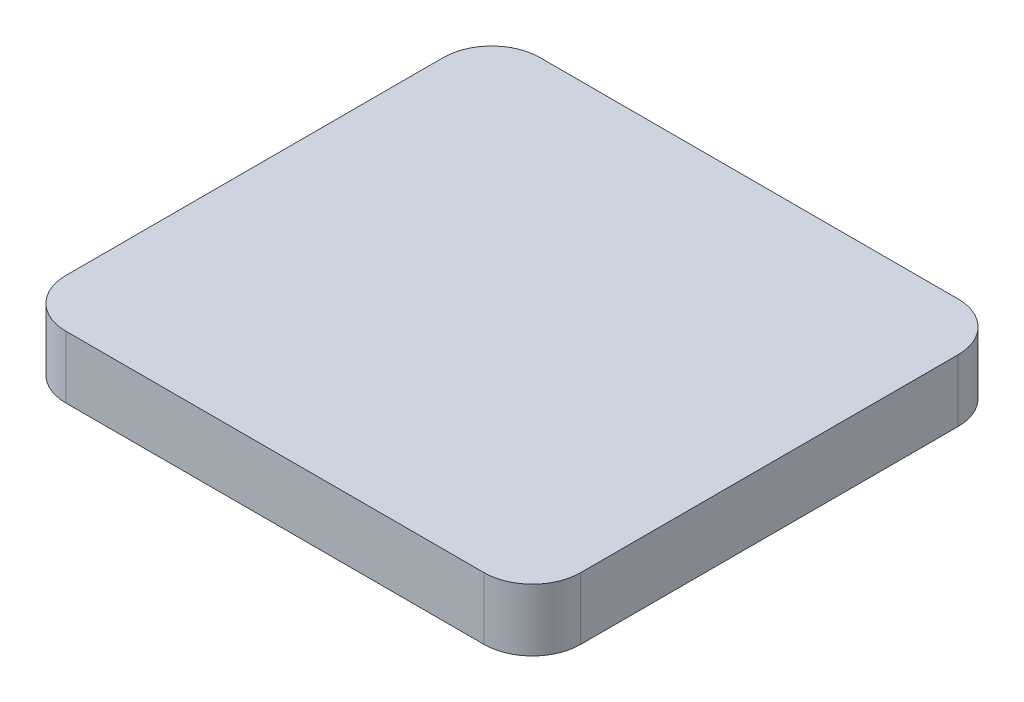
SolidWorks part; units mm, degrees
ref_plane "Front Plane" through (0, 0, 0) normal (0, 0, 1) x (1, 0, 0)
ref_plane "Top Plane" through (0, 0, 0) normal (0, 1, 0) x (1, 0, 0)
ref_plane "Right Plane" through (0, 0, 0) normal (1, 0, 0) x (0, 0, -1)
sketch "Sketch1" plane through (0, 0, 0) normal (0, 1, 0) x (1, 0, 0)
  line L0 (-22, 20.1) -> (-22, 22.1) construction
  line L1 (19.5, 20.1) -> (-19.5, 20.1)
  line L2 (22, 17.6) -> (22, -17.6)
  line L3 (19.5, -20.1) -> (-19.5, -20.1)
  line L4 (-22, 17.6) -> (-22, -17.6)
  line L5 (22, 20.1) -> (-22, -20.1) construction
  line L6 (22, -20.1) -> (-22, 20.1) construction
  line L7 (24, -22.1) -> (-24, -22.1)
  line L8 (24, -22.1) -> (24, 22.1)
  line L9 (24, 22.1) -> (-24, 22.1)
  line L10 (-24, -22.1) -> (-24, 22.1)
  line L11 (24, -22.1) -> (-24, 22.1) construction
  line L12 (24, 22.1) -> (-24, -22.1) construction
  line L13 (-22, 20.1) -> (-24, 20.1) construction
  arc A0 (-19.5, -20.1) -> (-22, -17.6) centre (-19.5, -17.6) cw
  arc A1 (22, -17.6) -> (19.5, -20.1) centre (19.5, -17.6) cw
  arc A2 (19.5, 20.1) -> (22, 17.6) centre (19.5, 17.6) cw
  arc A3 (-19.5, 20.1) -> (-22, 17.6) centre (-19.5, 17.6) ccw
  circle A4 centre (-19.5, 17.6) radius 4.5
  circle A5 centre (19.5, 17.6) radius 4.5
  circle A6 centre (19.5, -17.6) radius 4.5
  circle A7 centre (-19.5, -17.6) radius 4.5
  point P0 (0, 0)
  point P6 (0, 0)
  dimension "D4" = 2.5
  dimension "D1" = 44
  dimension "D2" = 40.2
  dimension "D3" = 2
extrude "Boss-Extrude1" add sketch "Sketch1" along normal blind 1.3 contours L1 A4 L4 A3 | A7 L4 A4 L10 | A7 L3 A0 L4 | A7 L7 A6 L3 | A6 L2 A1 L3 | A6 L8 A5 L2 | L2 A5 L1 A2 | A5 L9 A4 L1 region at (17.6292, 0, -20.2166) region at (0, 0, -21.1285) region at (-17.6292, 0, -20.2166) region at (23.0321, 0, 0) region at (23.3658, 0, 15.5336) region at (-23.0321, 0, 0) region at (0, 0, 21.1285) region at (-22.1166, 0, 15.7292)
sketch "Sketch2" plane through (0, 1.3, 0) normal (0, 1, 0) x (1, 0, 0)
  line L4 (-19.5, -22.1) -> (19.5, -22.1)
  line L5 (24, -17.6) -> (24, 17.6)
  line L6 (19.5, 22.1) -> (-19.5, 22.1)
  line L7 (-24, 17.6) -> (-24, -17.6)
  line L8 (-19.5, -22.1) -> (19.5, -22.1)
  line L9 (24, -17.6) -> (24, 17.6)
  line L10 (19.5, 22.1) -> (-19.5, 22.1)
  line L11 (-24, 17.6) -> (-24, -17.6)
  arc A4 (19.5, -22.1) -> (24, -17.6) centre (19.5, -17.6) ccw
  arc A5 (24, 17.6) -> (19.5, 22.1) centre (19.5, 17.6) ccw
  arc A6 (-19.5, 22.1) -> (-24, 17.6) centre (-19.5, 17.6) ccw
  arc A7 (-24, -17.6) -> (-19.5, -22.1) centre (-19.5, -17.6) ccw
  arc A8 (19.5, -22.1) -> (24, -17.6) centre (19.5, -17.6) ccw
  arc A9 (24, 17.6) -> (19.5, 22.1) centre (19.5, 17.6) ccw
  arc A10 (-19.5, 22.1) -> (-24, 17.6) centre (-19.5, 17.6) ccw
  arc A11 (-24, -17.6) -> (-19.5, -22.1) centre (-19.5, -17.6) ccw
  dimension "D1" = 0
extrude "Boss-Extrude2" add sketch "Sketch2" along normal blind 1.5
sketch "Sketch3" plane through (0, 1.3, 0) normal (0, -1, 0) x (1, 0, 0)
  line L0 (-24, 0) -> (24, 0) construction
  line L1 (-24, 17.6) -> (-24, -17.6) construction
  line L2 (24, 17.6) -> (24, -17.6) construction
  line L3 (-24, 11.05) -> (24, 11.05) construction
  line L4 (0, 11.05) -> (0, 22.1) construction
  line L5 (19.5, 22.1) -> (-19.5, 22.1) construction
  line L6 (0, 11.05) -> (0, 0) construction
  line L7 (-24, -11.05) -> (24, -11.05) construction
  line L8 (0, 0) -> (4.1348, 4.1348) construction
  line L9 (11.05, -24) -> (11.05, 24) construction
  line L10 (-11.05, -24) -> (-11.05, 24) construction
  line L11 (-22, -17.6) -> (-22, 17.6) construction
  line L12 (-22, -17.6) -> (-22, 17.6) construction
  line L13 (19.5, -20.1) -> (-19.5, -20.1) construction
  line L14 (22, -17.6) -> (22, 17.6) construction
  line L15 (19.5, 20.1) -> (-19.5, 20.1) construction
  line L16 (19.5, 20.1) -> (-19.5, 20.1) construction
  line L17 (0, 0) -> (0, -20.1) construction
  circle A0 centre (-22, 11.05) radius 0.4
  circle A1 centre (-22, 0) radius 0.4
  circle A2 centre (-22, -11.05) radius 0.4
  circle A3 centre (-11.05, -20.1) radius 0.4
  circle A4 centre (11.05, -20.1) radius 0.4
  circle A5 centre (22, -11.05) radius 0.4
  circle A6 centre (22, 0) radius 0.4
  circle A7 centre (22, 11.05) radius 0.4
  circle A8 centre (11.05, 20.1) radius 0.4
  circle A9 centre (0, 20.1) radius 0.4
  circle A10 centre (-11.05, 20.1) radius 0.4
  circle A11 centre (0, -20.1) radius 0.4
  dimension "D2" = 0.8
  dimension "D1" = 45
extrude "Boss-Extrude3" add sketch "Sketch3" along normal up to surface (1.3 mm away) up to face at (0, 0, 0)
sketch "Sketch4" plane through (0, 0, 0) normal (0, -1, 0) x (1, 0, 0)
  line L0 (-23, 17.6) -> (-23, -17.6)
  line L1 (-19.5, -21.1) -> (19.5, -21.1)
  line L2 (23, -17.6) -> (23, 17.6)
  line L3 (19.5, 21.1) -> (-19.5, 21.1)
  line L4 (19.5, 22.1) -> (-19.5, 22.1)
  line L5 (-24, 17.6) -> (-24, -17.6)
  line L6 (-19.5, -22.1) -> (19.5, -22.1)
  line L7 (24, -17.6) -> (24, 17.6)
  line L8 (19.5, 22.1) -> (-19.5, 22.1)
  line L9 (-24, 17.6) -> (-24, -17.6)
  line L10 (-19.5, -22.1) -> (19.5, -22.1)
  line L11 (24, -17.6) -> (24, 17.6)
  arc A0 (-19.5, 21.1) -> (-23, 17.6) centre (-19.5, 17.6) ccw
  arc A1 (-23, -17.6) -> (-19.5, -21.1) centre (-19.5, -17.6) ccw
  arc A2 (19.5, -21.1) -> (23, -17.6) centre (19.5, -17.6) ccw
  arc A3 (23, 17.6) -> (19.5, 21.1) centre (19.5, 17.6) ccw
  arc A4 (-19.5, 22.1) -> (-24, 17.6) centre (-19.5, 17.6) ccw
  arc A5 (-24, -17.6) -> (-19.5, -22.1) centre (-19.5, -17.6) ccw
  arc A6 (19.5, -22.1) -> (24, -17.6) centre (19.5, -17.6) ccw
  arc A7 (24, 17.6) -> (19.5, 22.1) centre (19.5, 17.6) ccw
  arc A8 (-19.5, 22.1) -> (-24, 17.6) centre (-19.5, 17.6) ccw
  arc A9 (-24, -17.6) -> (-19.5, -22.1) centre (-19.5, -17.6) ccw
  arc A10 (19.5, -22.1) -> (24, -17.6) centre (19.5, -17.6) ccw
  arc A11 (24, 17.6) -> (19.5, 22.1) centre (19.5, 17.6) ccw
  dimension "D1" = 0
  dimension "D2" = 1
extrude "Boss-Extrude4" add sketch "Sketch4" along normal blind 3
sketch "Sketch5" plane through (0, 1.3, 0) normal (0, -1, 0) x (1, 0, 0)
  line L16 (0.9798, -19.1) -> (10.0702, -19.1)
  line L17 (0.9798, -19.1) -> (10.0702, -19.1)
  line L31 (-12.0298, 19.1) -> (-19.5, 19.1)
  line L32 (-21, 17.6) -> (-21, 12.0298)
  line L33 (-21, 10.0702) -> (-21, 0.9798)
  line L34 (-21, -0.9798) -> (-21, -10.0702)
  line L35 (-21, -12.0298) -> (-21, -17.6)
  line L36 (-19.5, -19.1) -> (-12.0298, -19.1)
  line L37 (-10.0702, -19.1) -> (-0.9798, -19.1)
  line L38 (12.0298, -19.1) -> (19.5, -19.1)
  line L39 (21, -17.6) -> (21, -12.0298)
  line L40 (21, -10.0702) -> (21, -0.9798)
  line L41 (21, 0.9798) -> (21, 10.0702)
  line L42 (21, 12.0298) -> (21, 17.6)
  line L43 (19.5, 19.1) -> (12.0298, 19.1)
  line L44 (10.0702, 19.1) -> (0.9798, 19.1)
  line L45 (-0.9798, 19.1) -> (-10.0702, 19.1)
  line L46 (-12.0298, 19.1) -> (-19.5, 19.1)
  line L47 (-21, 17.6) -> (-21, 12.0298)
  line L48 (-21, 10.0702) -> (-21, 0.9798)
  line L49 (-21, -0.9798) -> (-21, -10.0702)
  line L50 (-21, -12.0298) -> (-21, -17.6)
  line L51 (-19.5, -19.1) -> (-12.0298, -19.1)
  line L52 (-10.0702, -19.1) -> (-0.9798, -19.1)
  line L53 (12.0298, -19.1) -> (19.5, -19.1)
  line L54 (21, -17.6) -> (21, -12.0298)
  line L55 (21, -10.0702) -> (21, -0.9798)
  line L56 (21, 0.9798) -> (21, 10.0702)
  line L57 (21, 12.0298) -> (21, 17.6)
  line L58 (19.5, 19.1) -> (12.0298, 19.1)
  line L59 (10.0702, 19.1) -> (0.9798, 19.1)
  line L60 (-0.9798, 19.1) -> (-10.0702, 19.1)
  arc A16 (0.9798, -19.1) -> (-0.9798, -19.1) centre (0, -20.1) ccw
  arc A17 (0.9798, -19.1) -> (-0.9798, -19.1) centre (0, -20.1) ccw
  arc A30 (-12.0298, 19.1) -> (-10.0702, 19.1) centre (-11.05, 20.1) ccw
  arc A31 (-19.5, 19.1) -> (-21, 17.6) centre (-19.5, 17.6) ccw
  arc A32 (-21, 10.0702) -> (-21, 12.0298) centre (-22, 11.05) ccw
  arc A33 (-21, -0.9798) -> (-21, 0.9798) centre (-22, 0) ccw
  arc A34 (-21, -12.0298) -> (-21, -10.0702) centre (-22, -11.05) ccw
  arc A35 (-21, -17.6) -> (-19.5, -19.1) centre (-19.5, -17.6) ccw
  arc A36 (-10.0702, -19.1) -> (-12.0298, -19.1) centre (-11.05, -20.1) ccw
  arc A37 (12.0298, -19.1) -> (10.0702, -19.1) centre (11.05, -20.1) ccw
  arc A38 (19.5, -19.1) -> (21, -17.6) centre (19.5, -17.6) ccw
  arc A39 (21, -10.0702) -> (21, -12.0298) centre (22, -11.05) ccw
  arc A40 (21, 0.9798) -> (21, -0.9798) centre (22, 0) ccw
  arc A41 (21, 12.0298) -> (21, 10.0702) centre (22, 11.05) ccw
  arc A42 (21, 17.6) -> (19.5, 19.1) centre (19.5, 17.6) ccw
  arc A43 (10.0702, 19.1) -> (12.0298, 19.1) centre (11.05, 20.1) ccw
  arc A44 (-0.9798, 19.1) -> (0.9798, 19.1) centre (0, 20.1) ccw
  arc A45 (-12.0298, 19.1) -> (-10.0702, 19.1) centre (-11.05, 20.1) ccw
  arc A46 (-19.5, 19.1) -> (-21, 17.6) centre (-19.5, 17.6) ccw
  arc A47 (-21, 10.0702) -> (-21, 12.0298) centre (-22, 11.05) ccw
  arc A48 (-21, -0.9798) -> (-21, 0.9798) centre (-22, 0) ccw
  arc A49 (-21, -12.0298) -> (-21, -10.0702) centre (-22, -11.05) ccw
  arc A50 (-21, -17.6) -> (-19.5, -19.1) centre (-19.5, -17.6) ccw
  arc A51 (-10.0702, -19.1) -> (-12.0298, -19.1) centre (-11.05, -20.1) ccw
  arc A52 (12.0298, -19.1) -> (10.0702, -19.1) centre (11.05, -20.1) ccw
  arc A53 (19.5, -19.1) -> (21, -17.6) centre (19.5, -17.6) ccw
  arc A54 (21, -10.0702) -> (21, -12.0298) centre (22, -11.05) ccw
  arc A55 (21, 0.9798) -> (21, -0.9798) centre (22, 0) ccw
  arc A56 (21, 12.0298) -> (21, 10.0702) centre (22, 11.05) ccw
  arc A57 (21, 17.6) -> (19.5, 19.1) centre (19.5, 17.6) ccw
  arc A58 (10.0702, 19.1) -> (12.0298, 19.1) centre (11.05, 20.1) ccw
  arc A59 (-0.9798, 19.1) -> (0.9798, 19.1) centre (0, 20.1) ccw
  dimension "D1" = 1
extrude "Cut-Extrude1" cut sketch "Sketch5" against normal blind 0.5
sketch "Sketch8" plane through (0, 0, 0) normal (0, -1, 0) x (1, 0, 0)
  line L0 (-11.05, 20.1) -> (-11.05, -20.1) construction
  line L1 (0, -20.1) -> (0, 20.1) construction
  line L2 (11.05, 20.1) -> (11.05, -20.1) construction
  line L3 (-22, 11.05) -> (22, 11.05) construction
  line L4 (22, 0) -> (-22, 0) construction
  line L5 (-22, -11.05) -> (22, -11.05) construction
  line L6 (19.5, 21.1) -> (-19.5, 21.1) construction
  line L7 (23, -17.6) -> (23, 17.6) construction
  line L8 (23, -17.6) -> (23, 17.6) construction
  line L9 (-19.5, -21.1) -> (19.5, -21.1) construction
  line L10 (-23, 17.6) -> (-23, -17.6) construction
  line L11 (-23, 17.6) -> (-23, -17.6) construction
  circle A0 centre (-11.05, 21.1) radius 0.4
  arc A1 (-11.45, 20.1) -> (-10.65, 20.1) centre (-11.05, 20.1) ccw construction
  circle A2 centre (0, 21.1) radius 0.4
  circle A3 centre (11.05, 21.1) radius 0.4
  circle A4 centre (23, 11.05) radius 0.4
  circle A5 centre (-23, 11.05) radius 0.4
  circle A6 centre (-23, 0) radius 0.4
  circle A7 centre (23, 0) radius 0.4
  circle A8 centre (23, -11.05) radius 0.4
  circle A9 centre (11.05, -21.1) radius 0.4
  circle A10 centre (0, -21.1) radius 0.4
  circle A11 centre (-11.05, -21.1) radius 0.4
  circle A12 centre (-23, -11.05) radius 0.4
  point P53 (0, 21)
  point P54 (11, 21)
  point P55 (22.9, 11)
  point P58 (22.9, 0)
  point P59 (22.9, -11)
  point P62 (11, -21)
  point P65 (0, -21)
  point P66 (-11, -21)
  point P67 (-11, -21)
  point P68 (-22.9, -11)
  point P71 (-22.9, 0)
  point P72 (-22.9, 11)
  point P73 (-22.9, 11)
extrude "Boss-Extrude5" add sketch "Sketch8" along normal up to surface (3 mm away) up to face at (0, -3, 0)
